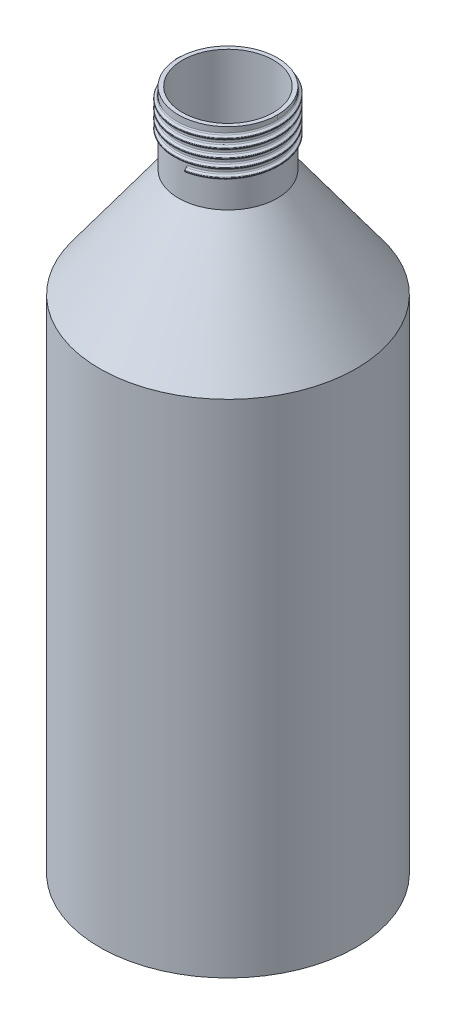
SolidWorks part; units mm, degrees
ref_plane "Front Plane" through (0, 0, 0) normal (0, 0, 1) x (1, 0, 0)
ref_plane "Top Plane" through (0, 0, 0) normal (0, 1, 0) x (1, 0, 0)
ref_plane "Right Plane" through (0, 0, 0) normal (1, 0, 0) x (0, 0, -1)
sketch "Sketch1" plane through (0, 0, 0) normal (0, 0, 1) x (1, 0, 0)
  line L0 (0, 0) -> (32, 0)
  line L1 (32, 0) -> (32, 125)
  line L2 (32, 125) -> (12.34, 152)
  line L3 (0, -1000) -> (0, 49000) construction
  line L4 (0, 152) -> (12.34, 152) construction
  line L5 (12.34, 152) -> (12.34, 170)
  line L6 (0, 1) -> (31, 1)
  line L7 (31, 1) -> (31, 124.6745)
  line L8 (31, 124.6745) -> (11.34, 151.6745)
  line L9 (11.34, 151.6745) -> (11.34, 170)
  line L10 (12.34, 170) -> (11.34, 170)
  line L11 (0, 0) -> (0, 1)
  dimension "D1" = 32
  dimension "D2" = 125
  dimension "D3" = 27
  dimension "D4" = 12.34
  dimension "D5" = 18
  dimension "D6" = 1
revolve "Revolve1" add sketch "Sketch1" angle 360 about L3
thread "Thread1" pitch 2.1167 method extrude profile "Thread Profile2" start angle 0, offset 0, length 10, pitch 2.1167, diameter 24.68
ref_plane "Plane2" through (-12.34, 170, 0) normal (0, 0, 1) x (-1, 0, 0)
sketch "Thread Profile2" plane through (-12.34, 170, 0) normal (0, 0, 1) x (-1, 0, 0)
  line L0 (0, 0) -> (0, 2.1167) construction
  line L1 (0, 0) -> (0, 1.5829)
  line L2 (0.381, 1.5829) -> (0.762, 1.5829) construction
  line L3 (0.762, 0.8497) -> (0.762, 0.7332)
  line L4 (0.6985, 0.9597) -> (0.1905, 1.253)
  line L5 (0.6985, 0.6232) -> (0.1905, 0.33)
  line L6 (0.381, 0) -> (0.762, 0) construction
  arc A0 (0.1905, 1.253) -> (0, 1.5829) centre (0.381, 1.5829) cw
  arc A1 (0.1905, 0.33) -> (0, 0) centre (0.381, 0) ccw
  arc A2 (0.762, 0.7332) -> (0.6985, 0.6232) centre (0.635, 0.7332) cw
  arc A3 (0.762, 0.8497) -> (0.6985, 0.9597) centre (0.635, 0.8497) ccw
  point P10 (0.762, 0.923)
  point P17 (0.762, 0.6599)
  point P18 (0, 1.363)
  point P19 (0, 0.22)
  point P20 (0, 0)
  dimension "RootFillet1" = 0.381
  dimension "RootFillet2" = 0.381
  dimension "CrestFillet2" = 0.127
  dimension "CrestFillet1" = 0.127
  dimension "Pitch" = 2.1167
  dimension "Angle1" = 30
  dimension "Angle2" = 30
  dimension "a" = 1.143
  dimension "b" = 0.762
  dimension "c" = 0.2631
